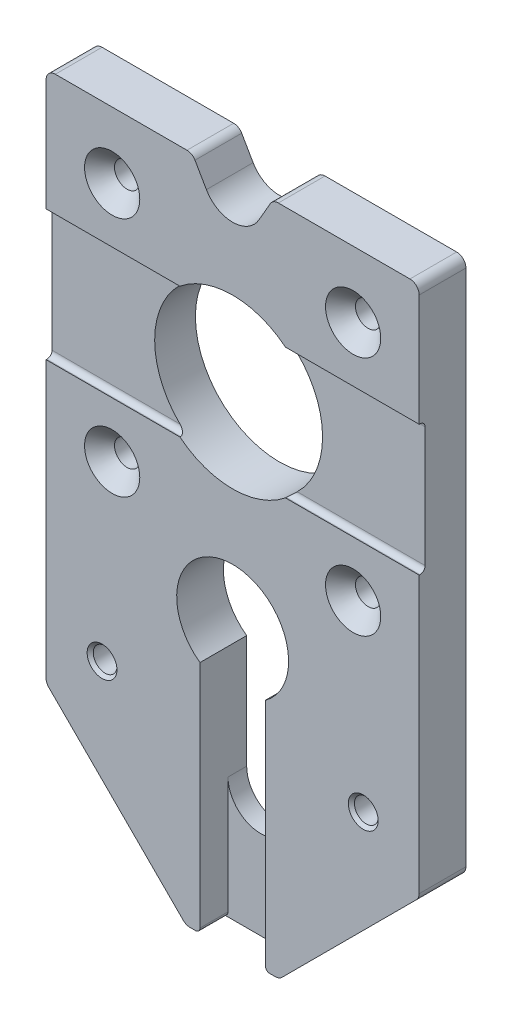
SolidWorks part; units mm, degrees
material "ASTM A36 Steel"
ref_plane "Front Plane" through (0, 0, 0) normal (0, 0, 1) x (1, 0, 0)
ref_plane "Top Plane" through (0, 0, 0) normal (0, 1, 0) x (1, 0, 0)
ref_plane "Right Plane" through (0, 0, 0) normal (1, 0, 0) x (0, 0, -1)
ref_axis "Axis1" through (0, 0, -8.3477) along (0, 0, 1)
sketch "Sketch1" plane through (0, 0, 0) normal (0, 0, 1) x (1, 0, 0)
  line L0 (5.5626, -42.657) -> (5.5626, -61.9125)
  line L1 (-31.75, 31.75) -> (31.75, 31.75)
  line L2 (-31.75, 31.75) -> (-31.75, -58.7248)
  line L3 (-7.9248, -82.55) -> (7.9248, -82.55)
  line L4 (31.75, 31.75) -> (31.75, -58.7248)
  line L5 (-5.5626, -61.9125) -> (-5.5626, -42.657)
  line L6 (31.75, -58.7248) -> (7.9248, -82.55)
  line L7 (-7.9248, -82.55) -> (-31.75, -58.7248)
  arc A0 (5.5626, -42.657) -> (-5.5626, -42.657) centre (0, -34.925) ccw
  arc A1 (5.5626, -61.9125) -> (-5.5626, -61.9125) centre (0, -61.9125) cw
  circle A2 centre (0, 0) radius 14.2875
  point P1 (0, -82.55)
  point P4 (0, 31.75)
  dimension "D4" = 19.05
  dimension "D7" = 26.9875
  dimension "D5" = 25.4
  dimension "D10" = 28.575
  dimension "D1" = 63.5
  dimension "D2" = 31.75
  dimension "D3" = 114.3
  dimension "D6" = 11.1252
  dimension "D8" = 45
  dimension "D9" = 23.8252
extrude "Boss-Extrude1" add sketch "Sketch1" against normal blind 7.9502
sketch "Sketch4" plane through (0, 0, 0) normal (0, 0, 1) x (1, 0, 0)
  line L0 (5.5626, -111.125) -> (5.5626, -34.925)
  line L1 (-5.5626, -34.925) -> (-5.5626, -111.125)
  line L2 (-5.5626, -111.125) -> (5.5626, -111.125)
  arc A0 (5.5626, -34.925) -> (-5.5626, -34.925) centre (0, -34.925) ccw
  dimension "D3" = 76.2
extrude "Cut-Extrude1" cut sketch "Sketch4" against normal blind 4.7752
hole_wizard "CSK for M4 Flat Head Machine Screw1" positions "Sketch3" profile "Sketch2" countersink size "M4" standard "Ansi Metric" end condition through all
sketch "Sketch3" plane through (0, 0, 0) normal (0, 0, 1) x (1, 0, 0)
  line L0 (5.7829, 0) -> (15.959, 0) construction
  line L1 (5.9608, 5.9608) -> (12.5748, 12.5748) construction
  point P0 (20.5061, 20.5061)
  dimension "D1" = 45
  dimension "D2" = 29
sketch "Sketch2" plane through (20.5061, 20.5061, 0) normal (1, 0, 0) x (0, -1, 0)
  line L0 (0, 0) -> (0, 7.9502)
  line L1 (0, 7.9502) -> (2.15, 7.9502)
  line L2 (2.15, 7.9502) -> (2.15, 2.55)
  line L3 (2.15, 2.55) -> (4.7, 0)
  line L5 (4.7, 0) -> (0, 0)
  line L6 (-2.15, 2.55) -> (-4.7, 0) construction
  line L11 (0, -6.35) -> (0, 107.95) construction
  dimension "Thru Hole Dia." = 4.3
  dimension "Thru Hole Depth" = 7.9502
  dimension "Near C'Sink Dia." = 9.4
  dimension "Near C'Sink Angle" = 90
pattern_circular "CirPattern1" count 4 over 360 about axis through (0, 0, -8.3477) along (0, 0, 1) of "CSK for M4 Flat Head Machine Screw1"
hole_wizard "#10-32 Tapped Hole1" positions "Sketch6" profile "Sketch7" tap size "#10-32" standard "Ansi Inch" end condition up to next
sketch "Sketch6" plane through (0, 0, 0) normal (0, 0, 1) x (1, 0, 0)
  point P0 (22.225, -50.8)
  point P1 (-22.225, -50.8)
  dimension "D1" = 22.225
  dimension "D2" = 22.225
  dimension "D3" = 50.8
sketch "Sketch7" plane through (22.225, -50.8, 0) normal (1, 0, 0) x (0, -1, 0)
  line L0 (0, 0) -> (0, 7.9502)
  line L1 (0, 7.9502) -> (2.54, 7.9502)
  line L2 (2.0193, 7.4295) -> (2.0193, 0.5207)
  line L3 (2.0193, 0.5207) -> (2.54, 0)
  line L5 (2.54, 0) -> (0, 0)
  line L6 (-2.0193, 0.5207) -> (-2.54, 0) construction
  line L7 (2.54, 7.9502) -> (2.0193, 7.4295)
  line L8 (-2.54, 7.9502) -> (-2.0193, 7.4295) construction
  line L11 (0, -6.35) -> (0, 107.95) construction
  dimension "Thread Major Dia." = 4.0386
  dimension "Thru Tap Drill Depth" = 7.9502
  dimension "Near C'Sink Dia." = 5.08
  dimension "Near C'Sink Angle" = 90
  dimension "Far C'Sink Dia." = 5.08
  dimension "Far C'Sink Angle" = 90
sketch "Sketch8" plane through (0, 0, 0) normal (0, 0, 1) x (1, 0, 0)
  line L0 (-4.4654, 27.5971) -> (-13.0623, 42.4873)
  line L1 (-13.0623, 42.4873) -> (13.0623, 42.4873)
  line L2 (13.0623, 42.4873) -> (4.4654, 27.5971)
  arc A0 (-4.4654, 27.5971) -> (4.4654, 27.5971) centre (0, 30.1752) ccw
  point P6 (0, 42.4873)
  dimension "D1" = 10.3124
  dimension "D3" = 80.9752
  dimension "D2" = 30.1752
  dimension "D4" = 60
extrude "Cut-Extrude2" cut sketch "Sketch8" against normal through all
fillet "Fillet1" radius 1.5748 8 edges at (6.8631, 31.75, -3.9751) (-6.8631, 31.75, -3.9751) (-31.75, -58.7248, -3.9751) (-7.9248, -82.55, -3.9751) (7.9248, -82.55, -3.9751) (31.75, -58.7248, -3.9751) (31.75, 31.75, -3.9751) (-31.75, 31.75, -3.9751)
fillet "Fillet2" radius 0.762 2 edges at (-5.5626, -82.55, -2.3876) (5.5626, -82.55, -2.3876)
pattern_linear "LPattern1" [suppressed] count 2 spacing 228.6 of bodies 108
sketch "Sketch9" [suppressed] plane through (0, 0, 0) normal (0, 0, 1) x (1, 0, 0)
  line L0 (0, 31.75) -> (0, -82.55)
  line L1 (30.1752, 31.75) -> (7.7723, 31.75) construction
  line L3 (6.3246, -82.55) -> (-6.3246, -82.55) construction
sketch "Sketch10" [suppressed] plane through (0, 0, 0) normal (0, 0, 1) x (1, 0, 0)
  line L0 (0, -198.4248) -> (0, -311.15)
  line L1 (6.3246, -311.15) -> (-6.3246, -311.15) construction
sketch "Sketch11" plane through (0, 0, -7.9502) normal (0, 0, -1) x (-1, 0, 0)
  line L0 (0, 30.1752) -> (0, -82.55)
  line L1 (7.2725, -82.55) -> (-7.2725, -82.55) construction
sketch "Sketch12" plane through (0, 0, 0) normal (0, 0, 1) x (1, 0, 0)
  line L1 (36.6783, 11.1125) -> (-36.5324, 11.1125)
  line L2 (36.6783, 11.1125) -> (36.6783, -11.1125)
  line L3 (36.6783, -11.1125) -> (-36.5324, -11.1125)
  line L4 (-36.5324, 11.1125) -> (-36.5324, -11.1125)
  dimension "D1" = 22.225
  dimension "D2" = 11.1125
extrude "Cut-Extrude3" cut sketch "Sketch12" against normal blind 1.016
fillet "Fillet3" radius 0.889 4 edges at (-20.3651, -11.1125, -1.016) (20.3651, -11.1125, -1.016) (20.3651, 11.1125, -1.016) (-20.3651, 11.1125, -1.016) tangent propagation no
